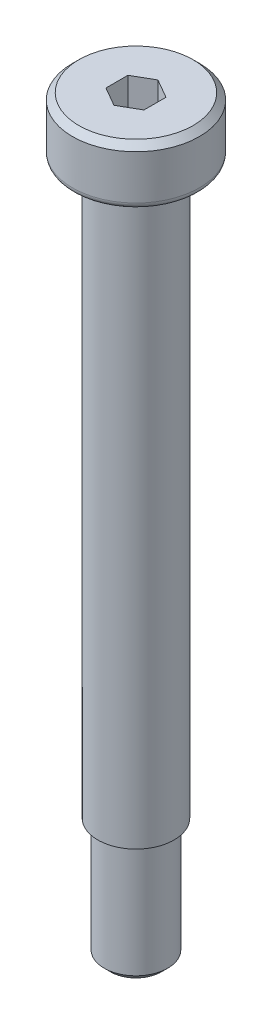
SolidWorks part; units mm, degrees
material "Plain Carbon Steel"
ref_plane "Front Plane" through (0, 0, 0) normal (0, 0, 1) x (1, 0, 0)
ref_plane "Top Plane" through (0, 0, 0) normal (0, 1, 0) x (1, 0, 0)
ref_plane "Right Plane" through (0, 0, 0) normal (1, 0, 0) x (0, 0, -1)
sketch "Sketch1" plane through (0, 0, 0) normal (0, 0, 1) x (1, 0, 0)
  line L0 (0, 0) -> (5, 0)
  line L1 (5, 0) -> (5, -4.5)
  line L2 (5, -4.5) -> (2.75, -4.5)
  line L3 (2.75, -4.5) -> (2.75, -5)
  line L4 (2.75, -5) -> (3, -5)
  line L5 (3, -5) -> (3, -49.5)
  line L6 (3, -49.5) -> (2.5, -49.5)
  line L7 (2.5, -49.5) -> (2.5, -59)
  line L8 (2.5, -59) -> (0, -59)
  line L9 (0, -59) -> (0, 0)
  line L10 (0, 5) -> (0, -64) construction
  dimension "D1" = 5
  dimension "D2" = 5
  dimension "D3" = 5
  dimension "D4" = 6
  dimension "D5" = 0.25
  dimension "D6" = 10
  dimension "Length" = 45
  dimension "D8" = 4.5
  dimension "D9" = 0.5
  dimension "D10" = 9.5
revolve "Revolve1" add sketch "Sketch1" angle 360 about L10
sketch "Sketch2" plane through (0, 0, 0) normal (0, 1, 0) x (1, 0, 0)
  line L1 (0, -1.7321) -> (1.5, -0.866)
  line L2 (1.5, -0.866) -> (1.5, 0.866)
  line L3 (1.5, 0.866) -> (0, 1.7321)
  line L4 (0, 1.7321) -> (-1.5, 0.866)
  line L5 (-1.5, 0.866) -> (-1.5, -0.866)
  line L6 (-1.5, -0.866) -> (0, -1.7321)
  circle A0 centre (0, 0) radius 1.5 construction
  dimension "D1" = 3
extrude "Cut-Extrude1" cut sketch "Sketch2" against normal blind 2.4
chamfer "Chamfer1" distance 0.5 angle 45 1 edges at (-5, 0, 0)
fillet "Fillet1" radius 0.5 1 edges at (-5, -4.5, 0)
chamfer "Chamfer2" distance 0.5 angle 45 1 edges at (-2.5, -59, 0)
